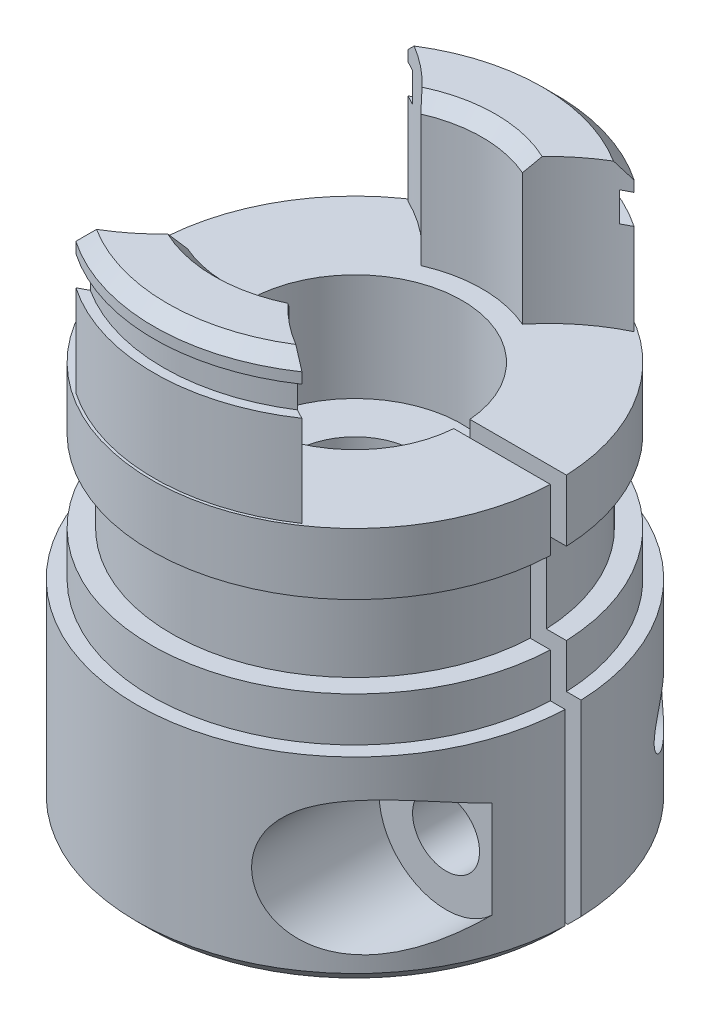
SolidWorks part; units mm, degrees
ref_plane "Front Plane" through (0, 0, 0) normal (0, 0, 1) x (1, 0, 0)
ref_plane "Top Plane" through (0, 0, 0) normal (0, 1, 0) x (1, 0, 0)
ref_plane "Right Plane" through (0, 0, 0) normal (1, 0, 0) x (0, 0, -1)
sketch "Sketch1" plane through (0, 0, 0) normal (0, 0, 1) x (1, 0, 0)
  line L0 (2.25, 9) -> (4, 9)
  line L1 (4, 9) -> (4, 0.5)
  line L2 (4, 0.5) -> (4.5, 0)
  line L3 (4.5, 0) -> (7.65, 0)
  line L4 (7.65, 0) -> (8.15, 0.5)
  line L5 (8.15, 0.5) -> (8.15, 7.5)
  line L6 (8.15, 7.5) -> (7.6, 7.5)
  line L7 (7.6, 7.5) -> (7.6, 9.15)
  line L8 (7.6, 9.15) -> (6.85, 9.15)
  line L9 (6.85, 9.15) -> (6.85, 12.2)
  line L10 (6.85, 12.2) -> (7.6, 12.2)
  line L11 (7.6, 12.2) -> (7.6, 14.5)
  line L12 (7.6, 14.5) -> (4, 14.5)
  line L13 (4, 14.5) -> (4, 10.5)
  line L14 (4, 10.5) -> (2.25, 10.5)
  line L15 (2.25, 10.5) -> (2.25, 9)
  line L16 (0, 0) -> (0, 14.5) construction
revolve "Revolve1" add sketch "Sketch1" angle 360 about L16 reverse direction yes
sketch "Sketch2" plane through (0, 0, 0) normal (1, 0, 0) x (0, 0, -1)
  line L0 (4.75, 14.5) -> (7.5, 14.5)
  line L1 (7.5, 14.5) -> (7.5, 17.9)
  line L2 (7.5, 17.9) -> (7.15, 17.9)
  line L3 (7.15, 17.9) -> (7.15, 19)
  line L4 (7.15, 19) -> (7.5, 19)
  line L5 (7.5, 19) -> (7.5, 19.4)
  line L6 (7.5, 19.4) -> (7, 19.9)
  line L7 (7, 19.9) -> (5.25, 19.9)
  line L8 (5.25, 19.9) -> (4.75, 19.4)
  line L9 (4.75, 19.4) -> (4.75, 14.5)
  line L10 (0, 14.5) -> (0, 20) construction
revolve "Revolve2" add sketch "Sketch2" angle 360 about L10 reverse direction yes
ref_plane "Plane1" through (0, 14.5, 0) normal (0, 1, 0) x (1, 0, 0)
sketch "Sketch3" plane through (0, 14.5, 0) normal (0, 1, 0) x (1, 0, 0)
  circle A0 centre (7.25, 0) radius 6.9
extrude "Cut-Extrude1" cut sketch "Sketch3" along normal blind 6
sketch "Sketch4" plane through (0, 14.5, 0) normal (0, 1, 0) x (1, 0, 0)
  circle A0 centre (-7.25, 0) radius 6.9
extrude "Cut-Extrude2" cut sketch "Sketch4" along normal blind 6
ref_plane "Plane2" through (0, 3.6, 0) normal (0, 1, 0) x (1, 0, 0)
sketch "Sketch5" plane through (0, 3.6, 0) normal (0, 1, 0) x (1, 0, 0)
  line L0 (6, 6.55) -> (7.0065, 6.55)
  line L1 (7.0065, 6.55) -> (7.0065, 0.3)
  line L2 (7.0065, 0.3) -> (7.25, 0.3)
  line L3 (7.25, 0.3) -> (7.25, -2.6)
  line L4 (7.25, -2.6) -> (8.5, -2.6)
  line L5 (8.5, -2.6) -> (8.5, -8.15)
  line L6 (8.5, -8.15) -> (6, -8.15)
  line L7 (6, -8.15) -> (6, 6.55)
  line L8 (6, -8.15) -> (6, 6.55) construction
revolve "Cut-Revolve1" cut sketch "Sketch5" angle 360 about L8 reverse direction yes
cosmetic thread "Cosmetic Thread1" parameters "D1"=3.842, "D2"=2.5
sketch "Sketch6" plane through (0, 0, 0) normal (1, 0, 0) x (0, 0, -1)
  line L0 (-0.3, 19.9) -> (-0.3, 0)
  line L1 (-0.3, 0) -> (0.3, 0)
  line L2 (0.3, 0) -> (0.3, 19.9)
  arc A0 (0.3, 19.9) -> (-0.3, 19.9) centre (0, 19.9) ccw
extrude "Cut-Extrude3" cut sketch "Sketch6" along normal blind 8.15
ref_plane "Plane3" through (0, 0, 0) normal (0, 1, 0) x (1, 0, 0)
ref_plane "Plane4" through (0, 19.9, 0) normal (0, 1, 0) x (1, 0, 0)
ref_plane "Plane5" through (0, 10.5, 0) normal (0, 1, 0) x (1, 0, 0)
ref_plane "Plane6" through (0, 0, 2.6) normal (0, 0, 1) x (1, 0, 0)
ref_plane "Plane7" through (0, 0, 0) normal (1, 0, 0) x (0, 0, -1)
ref_plane "ANBAU XY" through (0, 0, 0) normal (0, -1, 0) x (-1, 0, 0)
ref_plane "ANBAU XZ" through (0, 0, 0) normal (0, 0, -1) x (-1, 0, 0)
ref_plane "ANBAU YZ" through (0, 0, 0) normal (1, 0, 0) x (0, 0, -1)
ref_axis "ANBAU X" through (-80.9, 0, 0) along (1, 0, 0)
ref_axis "ANBAU Y" through (0, 0, -50) along (0, 0, 1)
ref_axis "ANBAU Z" through (0, -50, 0) along (0, 1, 0)
sketch3d "ANBAU"
  point P0 (0, 0, 0)
ref_plane "DIN_1 XY" through (0, 0, 2.6) normal (0, 0, 1) x (1, 0, 0)
ref_plane "DIN_1 XZ" through (0, 3.6, 0) normal (0, -1, 0) x (-1, 0, 0)
ref_plane "DIN_1 YZ" through (6, 0, 0) normal (1, 0, 0) x (0, 0, -1)
ref_axis "DIN_1 X" through (-80.9, 3.6, 2.6) along (1, 0, 0)
ref_axis "DIN_1 Y" through (6, -50, 2.6) along (0, 1, 0)
ref_axis "DIN_1 Z" through (6, 3.6, 80.9) along (0, 0, -1)
sketch3d "DIN_1"
  point P0 (6, 3.6, 2.6)
ref_plane "DIN_2 XY" through (0, 10.5, 0) normal (0, 1, 0) x (1, 0, 0)
ref_plane "DIN_2 XZ" through (0, 0, 0) normal (0, 0, 1) x (1, 0, 0)
ref_plane "DIN_2 YZ" through (0, 0, 0) normal (1, 0, 0) x (0, 0, -1)
ref_axis "DIN_2 X" through (-80.9, 10.5, 0) along (1, 0, 0)
ref_axis "DIN_2 Y" through (0, 10.5, 50) along (0, 0, -1)
ref_axis "DIN_2 Z" through (0, 50, 0) along (0, -1, 0)
sketch3d "DIN_2"
  point P0 (0, 10.5, 0)
other "Freeze***"
